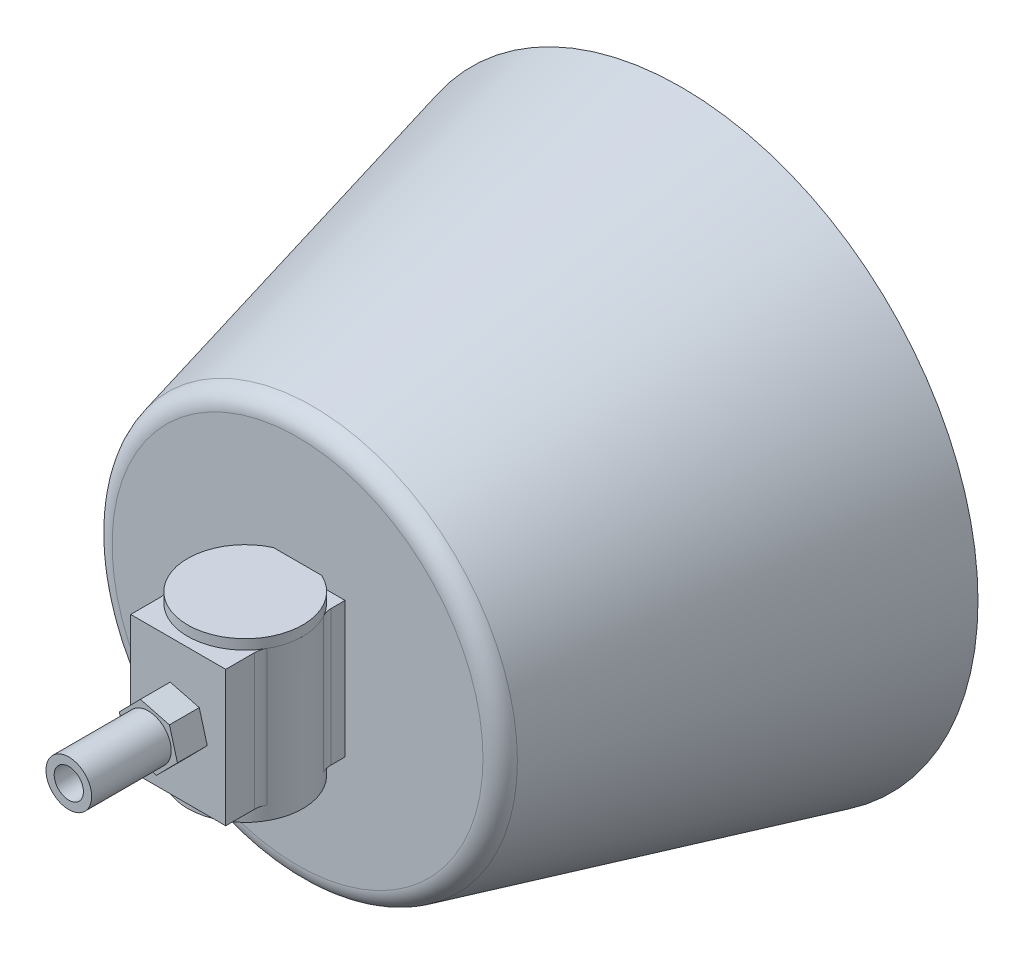
SolidWorks part; units mm, degrees
ref_plane "Front Plane" through (0, 0, 0) normal (0, 0, 1) x (1, 0, 0)
ref_plane "Top Plane" through (0, 0, 0) normal (0, 1, 0) x (1, 0, 0)
ref_plane "Right Plane" through (0, 0, 0) normal (1, 0, 0) x (0, 0, -1)
sketch "Sketch1" plane through (0, 0, 0) normal (0, 1, 0) x (1, 0, 0)
  line L0 (0, 0) -> (-25.6688, 0)
  line L1 (-25.6688, 0) -> (-37.8719, 49.0231)
  line L2 (-37.8719, 49.0231) -> (-35.3745, 49.0231)
  line L3 (-35.3745, 49.0231) -> (-23.9746, 3.227)
  line L4 (-23.9746, 3.227) -> (0, 3.227)
  line L5 (0, 3.227) -> (0, 0)
revolve "Revolve1" add sketch "Sketch1" angle 360 about L5
sketch "Sketch2" plane through (0, 0, 0) normal (0, 0, 1) x (1, 0, 0)
  line L1 (-6.0698, -8.6565) -> (6.0698, -8.6565)
  line L2 (-6.0698, -8.6565) -> (-6.0698, 8.6565)
  line L3 (-6.0698, 8.6565) -> (6.0698, 8.6565)
  line L4 (6.0698, -8.6565) -> (6.0698, 8.6565)
  line L5 (-6.0698, -8.6565) -> (6.0698, 8.6565) construction
  line L6 (-6.0698, 8.6565) -> (6.0698, -8.6565) construction
  point P0 (0, 0)
extrude "Boss-Extrude1" add sketch "Sketch2" along normal blind 15.24
sketch "Sketch3" plane through (0, 8.6565, 0) normal (0, 1, 0) x (1, 0, 0)
  circle A0 centre (0, -6.6797) radius 7.3549
extrude "Boss-Extrude2" add sketch "Sketch3" along normal blind 1.27
sketch "Sketch4" plane through (0, 8.6565, 0) normal (0, -1, 0) x (1, 0, 0)
  circle A0 centre (0.0107, 6.6776) radius 7.344
extrude "Boss-Extrude3" add sketch "Sketch4" along normal blind 19.05
fillet "Fillet1" radius 5.08 1 edges at (-23.9746, 0, -3.227)
fillet "Fillet2" radius 2.54 1 edges at (-25.6688, 0, 0)
sketch "Sketch5" plane through (0, 0, 15.24) normal (0, 0, 1) x (1, 0, 0)
  circle A0 centre (0, 0) radius 2.9178
extrude "Boss-Extrude4" add sketch "Sketch5" along normal blind 13.97
sketch "Sketch6" plane through (0, 0, 15.24) normal (0, 0, 1) x (1, 0, 0)
  line L1 (1.0224, -3.6954) -> (3.7115, -0.9623)
  line L2 (3.7115, -0.9623) -> (2.6891, 2.7331)
  line L3 (2.6891, 2.7331) -> (-1.0224, 3.6954)
  line L4 (-1.0224, 3.6954) -> (-3.7115, 0.9623)
  line L5 (-3.7115, 0.9623) -> (-2.6891, -2.7331)
  line L6 (-2.6891, -2.7331) -> (1.0224, -3.6954)
  circle A0 centre (0, 0) radius 3.3205 construction
extrude "Boss-Extrude5" add sketch "Sketch6" along normal blind 3.81
fillet "Fillet3" radius 2.54 4 edges at (6.0698, 0, 2.5277) (6.0698, 0, 10.8274) (-6.0698, 0, 2.5591) (-6.0698, 0, 10.7961)
sketch "Sketch8" plane through (0, 0, -3.227) normal (0, 0, -1) x (-1, 0, 0)
  circle A0 centre (0, 0) radius 1.8666
extrude "Cut-Extrude1" cut sketch "Sketch8" against normal blind 54.61
fillet "Fillet4" radius 2.54 1 edges at (-1.8666, 0, -3.227)
